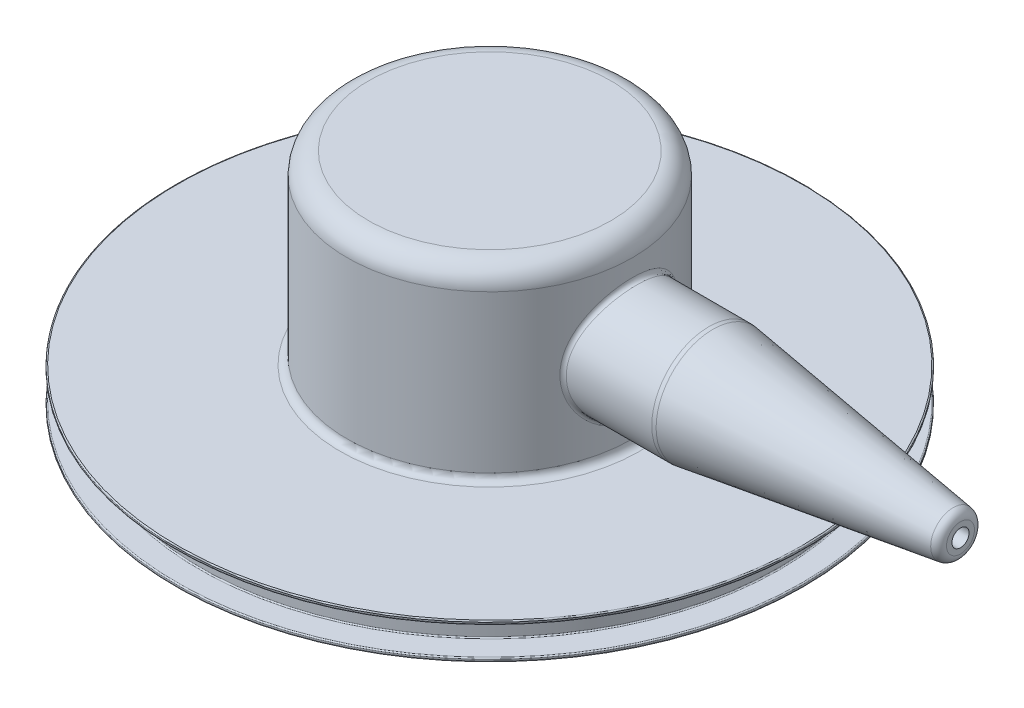
SolidWorks part; units mm, degrees
ref_plane "front" through (0, 0, 0) normal (0, 0, 1) x (1, 0, 0)
ref_plane "top" through (0, 0, 0) normal (0, 1, 0) x (1, 0, 0)
ref_plane "right" through (0, 0, 0) normal (1, 0, 0) x (0, 0, -1)
sketch "Sketch1" plane through (0, 0, 0) normal (0, 0, 1) x (1, 0, 0)
  line L0 (0, 16) -> (0, 0)
  line L13 (0, 16) -> (10, 16)
  line L20 (0, 0) -> (19, 0)
  line L21 (19, 0) -> (22, 0.5)
  line L22 (22, 0.5) -> (22, 0.75)
  line L23 (22, 0.75) -> (20.2748, 0.75)
  line L24 (20.2748, 0.75) -> (20.2748, 2.75)
  line L25 (20.2748, 2.75) -> (22, 2.75)
  line L26 (22, 2.75) -> (22, 3)
  line L27 (10, 16) -> (10, 3)
  line L28 (10, 3) -> (22, 3)
  point P2 (20.2748, 2.75)
  point P4 (19, 0)
  point P7 (22, 0.75)
  point P10 (22, 0.5)
  point P12 (22, 0)
  point P13 (0, 0)
  point P16 (22, 3)
  dimension "D1" = 10
  dimension "D2" = 3
  dimension "D3" = 3
  dimension "D4" = 0.25
  dimension "D5" = 0.25
  dimension "D6" = 0.5
  dimension "D7" = 16
revolve "Revolve1" add sketch "Sketch1" angle 360 about L0
sketch "Sketch3" plane through (0, 0, 0) normal (1, 0, 0) x (0, 0, -1)
  line L0 (0, 0) -> (0, 64.7736) construction
  circle A0 centre (0, 9) radius 4
  circle A1 centre (0, 9) radius 3
  dimension "D1" = 9
  dimension "D2" = 8
  dimension "D3" = 6
extrude "Boss-Extrude1" add sketch "Sketch3" along normal blind 25 contours A0
extrude "Boss-Extrude2" add sketch "Sketch3<5>" along normal blind 8 from surface contours A1 starting at face at (25, 9, -4)
sketch "Sketch3<5>" plane through (0, 0, 0) normal (1, 0, 0) x (0, 0, -1) same geometry as "Sketch3"
sketch "Sketch11" plane through (0, 0, 0) normal (0, 0, 1) x (1, 0, 0)
  line L0 (0, 4) -> (0, 0)
  line L2 (0, 0) -> (19, 0)
  line L4 (0, 0) -> (0, 4.7847) construction
  arc A1 (0, 4) -> (19, 0) centre (-0.6724, -46.3191) cw
  dimension "D1" = 4
  dimension "D2" = 19
revolve "Cut-Revolve10" cut sketch "Sketch11" angle 360 about L4
sketch "Sketch15" plane through (0, 0, 0) normal (0, 1, 0) x (1, 0, 0)
  circle A0 centre (0, 0) radius 1.8
  dimension "D1" = 3.6
extrude "Cut-Extrude1" cut sketch "Sketch15" along normal blind 11.8 and the other way through all
sketch "Sketch16" plane through (0, 0, 0) normal (0, 0, 1) x (1, 0, 0)
  line L0 (33, 12) -> (33, 13.5)
  line L1 (33, 6) -> (33, 12) construction
  line L3 (25, 5) -> (25, 13) construction
  line L5 (33, 9) -> (25, 9) construction
  line L7 (25, 13) -> (10, 13) construction
  line L8 (15.5034, 13) -> (33, 13.5)
  line L9 (15.5034, 13) -> (33, 13)
  line L10 (33, 13) -> (33, 12)
sketch "Sketch19" plane through (0, 0, 0) normal (0, 0, 1) x (1, 0, 0)
  line L0 (25, 13) -> (10, 13) construction
  line L1 (33, 13) -> (15.5, 13)
  line L2 (33, 13) -> (33, 10.5)
  line L3 (15.5, 13) -> (33, 10.5)
  line L4 (33, 9) -> (44.2045, 9) construction
  point P0 (33, 12)
  point P1 (25, 13)
  point P3 (33, 13)
  point P5 (15.5, 13)
  point P6 (33, 9)
  dimension "D1" = 17.5
  dimension "D2" = 2.5
  dimension "D3" = 4
revolve "Cut-Revolve14" cut sketch "Sketch19" angle 360 about L4
sketch "Sketch17" plane through (0, 0, 0) normal (0, 0, 1) x (1, 0, 0)
  line L1 (33, 9.6) -> (33, 9)
  line L3 (1.8027, 9) -> (1.8027, 11.8)
  line L5 (1.8027, 11.8) -> (15.5034, 11.8)
  line L8 (1.8027, 9) -> (33, 9)
  line L10 (1.8027, 9) -> (42.1221, 9) construction
  line L15 (15.5034, 11.8) -> (30.9004, 9.6)
  line L18 (33, 9.6) -> (30.9004, 9.6)
  dimension "D1" = 30.9004
  dimension "D2" = 9.6
  dimension "D4" = 33
revolve "Cut-Revolve13" cut sketch "Sketch17" angle 360 about L10
fillet "Fillet1" radius 0.5 1 edges at (-10, 3, 0)
fillet "Fillet2" radius 0.3 1 edges at (9.184, 9.5886, -3.9565)
fillet "Fillet3" radius 2 1 edges at (15.5, 9, 4)
fillet "Fillet4" radius 1.5 1 edges at (-10, 16, 0)
fillet "Fillet5" radius 0.5 1 edges at (0, 0, -19)
fillet "Fillet6" radius 0.08 6 edges at (-20.2748, 2.75, 0) (-20.2748, 0.75, 0) (-22, 0.5, 0) (-22, 0.75, 0) (-22, 2.75, 0) (-22, 3, 0)
fillet "Fillet7" radius 0.08 1 edges at (0, 3.9437, -1.8)
fillet "Fillet8" radius 0.6 1 edges at (33, 9, 1.5)
